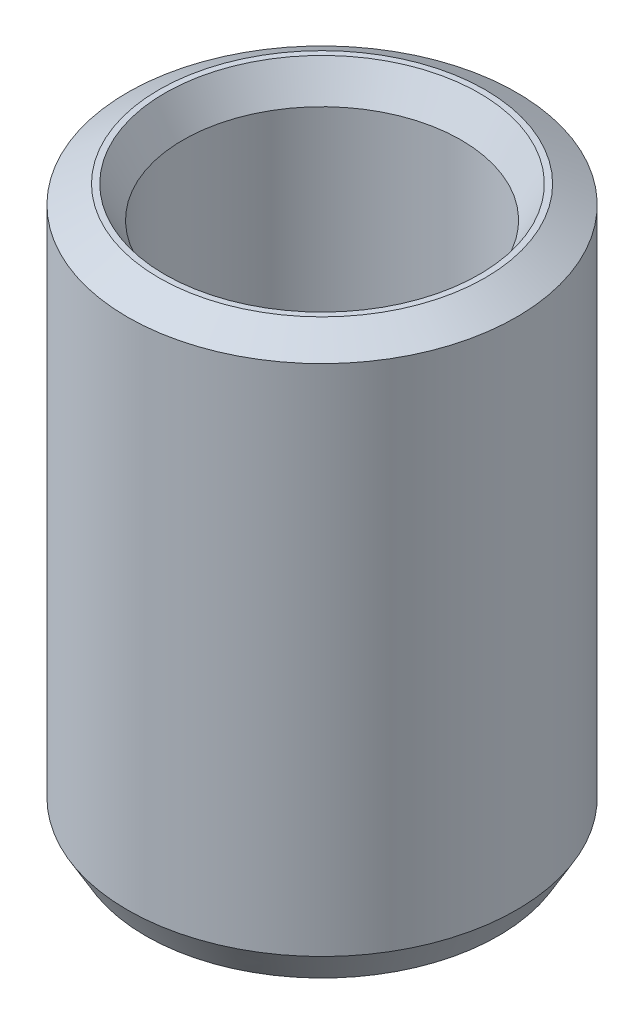
SolidWorks part; units mm, degrees
ref_plane "Front Plane" through (0, 0, 0) normal (0, 0, 1) x (1, 0, 0)
ref_plane "Top Plane" through (0, 0, 0) normal (0, 1, 0) x (1, 0, 0)
ref_plane "Right Plane" through (0, 0, 0) normal (1, 0, 0) x (0, 0, -1)
sketch "Sketch1" plane through (0, 0, 0) normal (0, 1, 0) x (1, 0, 0)
  circle A0 centre (0, 0) radius 22.5
  dimension "SLEEVE_OD" = 45
extrude "Boss-Extrude1" add sketch "Sketch1" along normal blind 65.1271
sketch "Sketch2" plane through (0, 0, 0) normal (0, 1, 0) x (1, 0, 0)
  circle A0 centre (0, 0) radius 16.0745
  dimension "BORE_D" = 32.1489
extrude "Cut-Extrude1" cut sketch "Sketch2" along normal through all
chamfer "Chamfer1" distance 2.1047 angle 60 4 edges at (0, 65.1271, 16.0745) (0, 0, 16.0745) (0, 0, 22.5) (0, 65.1271, 22.5) first distance on face at (0, 65.1271, 16.0745) first distance on face at (0, 0, 16.0745) first distance on face at (0, 65.1271, 22.5)
